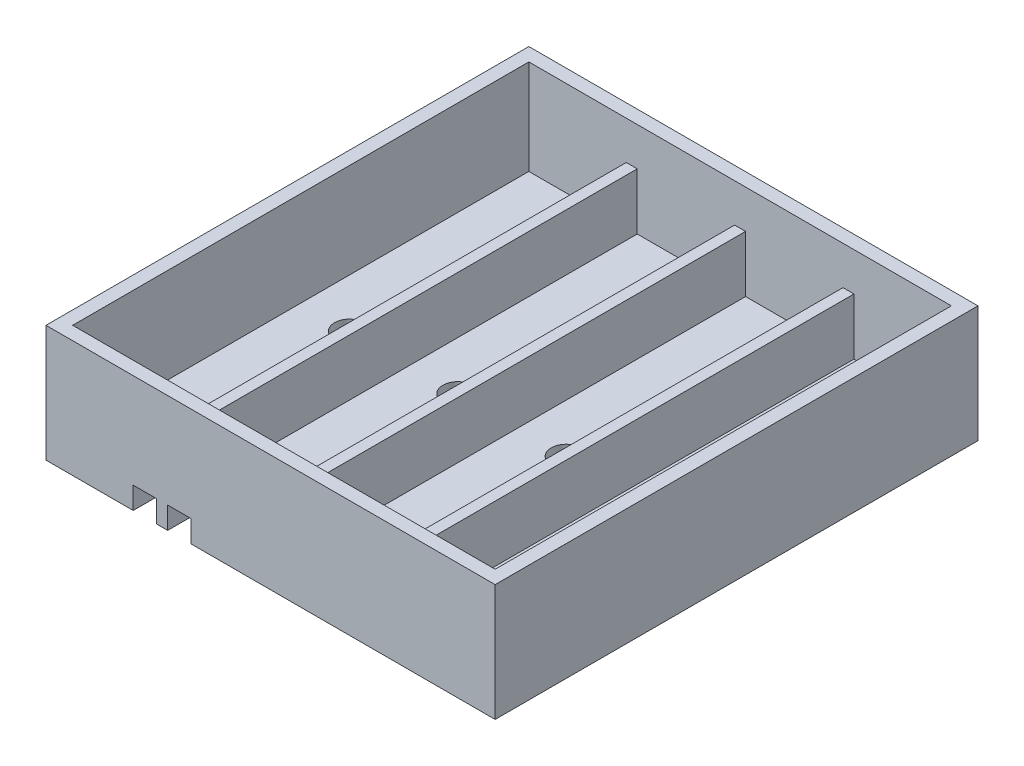
SolidWorks part; units mm, degrees
ref_plane "前视基准面" through (0, 0, 0) normal (0, 0, 1) x (1, 0, 0)
ref_plane "上视基准面" through (0, 0, 0) normal (0, 1, 0) x (1, 0, 0)
ref_plane "右视基准面" through (0, 0, 0) normal (1, 0, 0) x (0, 0, -1)
other "Configuration Table"
sketch "草图1" plane through (0, 0, 0) normal (0, 1, 0) x (1, 0, 0)
  line L0 (-26.95, 30.8) -> (-26.95, -30.8)
  line L1 (-28.65, -30.8) -> (28.65, -30.8)
  line L2 (-28.65, -30.8) -> (-28.65, 30.8)
  line L3 (-28.65, 30.8) -> (28.65, 30.8)
  line L4 (28.65, -30.8) -> (28.65, 30.8)
  line L5 (-28.65, -30.8) -> (28.65, 30.8) construction
  line L6 (-28.65, 30.8) -> (28.65, -30.8) construction
  line L39 (-17.525, -30.8) -> (-14.525, -30.8)
  line L40 (-17.525, -30.8) -> (-17.525, -24)
  line L41 (-17.525, -24) -> (-14.525, -24)
  line L42 (-14.525, -30.8) -> (-14.525, -24)
  line L43 (-13.125, -30.8) -> (-10.125, -30.8)
  line L44 (-13.125, -30.8) -> (-13.125, -24)
  line L45 (-13.125, -24) -> (-10.125, -24)
  line L46 (-10.125, -30.8) -> (-10.125, -24)
  line L47 (-14.525, 30.8) -> (-13.125, 30.8)
  line L48 (-14.525, 30.8) -> (-14.525, -30.8)
  line L49 (-14.525, -30.8) -> (-13.125, -30.8)
  line L50 (-13.125, 30.8) -> (-13.125, -30.8)
  line L55 (13.125, 30.8) -> (14.525, 30.8)
  line L56 (13.125, 30.8) -> (13.125, -30.8)
  line L57 (13.125, -30.8) -> (14.525, -30.8)
  line L58 (14.525, 30.8) -> (14.525, -30.8)
  line L59 (26.95, 30.8) -> (26.95, -30.8)
  line L60 (-26.95, 0) -> (-14.525, 0)
  line L61 (-13.125, 0) -> (-0.7, 0)
  line L62 (0.7, 0) -> (13.125, 0)
  line L63 (14.525, 0) -> (26.95, 0)
  line L65 (-0.7, 30.8) -> (0.7, 30.8)
  line L66 (-0.7, 30.8) -> (-0.7, -30.8)
  line L67 (-0.7, -30.8) -> (0.7, -30.8)
  line L68 (0.7, 30.8) -> (0.7, -30.8)
  circle A0 centre (-20.7375, 0) radius 1.9
  circle A1 centre (-6.9125, 0) radius 1.9
  circle A2 centre (6.9125, 0) radius 1.9
  circle A3 centre (20.7375, 0) radius 1.9
  point P13 (-14.525, -27.4)
  dimension "D1" = 61.6
  dimension "D2" = 3
  dimension "D7" = 1.4
  dimension "D5" = 1.4
  dimension "D6" = 6.8
  dimension "D10" = 3.8
  dimension "D3" = 57.3
  dimension "D8" = 1.7
  dimension "D9" = 1.7
extrude "凸台-拉伸1" add sketch "草图1" along normal blind 2.8 contours L2 L3 L4 L1
extrude "拉伸-薄壁1" add sketch "草图1<11>" along normal blind 14.9 thin contours L2 L3 L4 L1 thin type one direction reverse wall 1.7
sketch "草图1<11>" plane through (0, 0, 0) normal (0, 1, 0) x (1, 0, 0) same geometry as "草图1"
extrude "切除-拉伸1" cut sketch "草图1<13>" along normal up to surface (2.8 mm away) contours L40 L41 L42 L39 | L44 L45 L46 L43 up to face at (0, 2.8, 0)
sketch "草图1<13>" plane through (0, 0, 0) normal (0, 1, 0) x (1, 0, 0) same geometry as "草图1"
extrude "凸台-拉伸2" add sketch "草图1<14>" along normal blind 10 contours L48 L49 L50 L47 | L66 L67 L68 L65 | L56 L57 L58 L55
sketch "草图1<14>" plane through (0, 0, 0) normal (0, 1, 0) x (1, 0, 0) same geometry as "草图1"
extrude "切除-拉伸2" cut sketch "草图1<15>" along normal through all contours A0 | A1 | A2 | A3
sketch "草图1<15>" plane through (0, 0, 0) normal (0, 1, 0) x (1, 0, 0) same geometry as "草图1"
